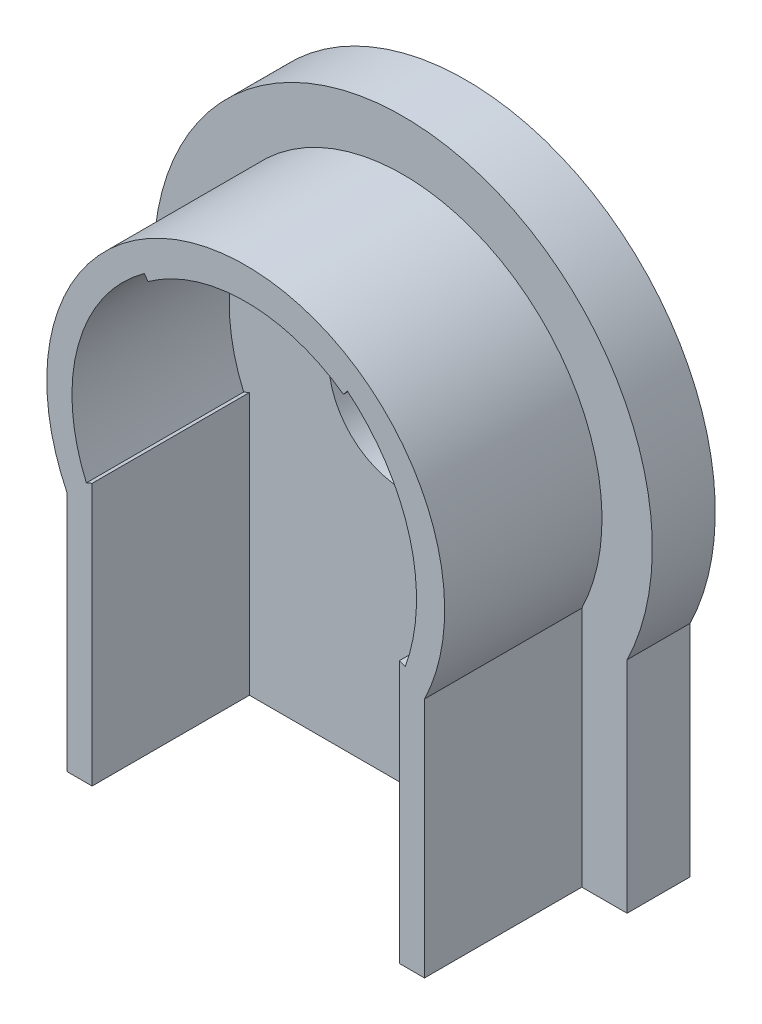
SolidWorks part; units mm, degrees
ref_plane "Alzado" through (0, 0, 0) normal (0, 0, 1) x (1, 0, 0)
ref_plane "Planta" through (0, 0, 0) normal (0, 1, 0) x (1, 0, 0)
ref_plane "Vista lateral" through (0, 0, 0) normal (1, 0, 0) x (0, 0, -1)
sketch "Croquis1" plane through (0, 0, 0) normal (0, 0, 1) x (1, 0, 0)
  line L0 (-7.75, -16.5939) -> (7.75, -16.5939)
  line L1 (-7.75, -16.5939) -> (-7.75, -8.4659)
  line L2 (7.75, -16.5939) -> (7.75, -8.2)
  line L4 (-7.75, -8.4659) -> (-7.75, -3.3658)
  line L5 (7.75, -8.2) -> (7.75, -3.3658)
  line L6 (-9.02, -8.4659) -> (-9.02, -4.4019)
  line L7 (9.02, -16.5939) -> (9.02, -8.2)
  line L9 (-9.02, -16.5939) -> (-9.02, -8.4659)
  line L10 (9.02, -8.2) -> (9.02, -4.4019)
  line L11 (-9.02, -8.4659) -> (-9.02, -3.3658) construction
  line L12 (-7.75, -16.5939) -> (-9.02, -16.5939)
  line L13 (7.75, -16.5939) -> (9.02, -16.5939)
  line L14 (-9.02, -17.8639) -> (-9.02, -8.4659) construction
  line L15 (-9.02, -17.8639) -> (9.02, -17.8639) construction
  line L16 (9.02, -17.8639) -> (9.02, -8.2) construction
  line L17 (0, 0) -> (0, -33.1879) construction
  arc A0 (7.75, -3.3658) -> (-7.75, -3.3658) centre (0, 0) ccw
  arc A1 (9.02, -4.4019) -> (-9.02, -4.4019) centre (0, 0) ccw
  circle A2 centre (0, 0) radius 8.4493 construction
  circle A3 centre (0, 0) radius 10.0368 construction
  point P5 (0, -8.4493)
  point P18 (0, -16.5939)
  dimension "D1" = 16.8986
  dimension "D3" = 15.5
  dimension "D4" = 8.128
  dimension "D5" = 1.27
  dimension "D6" = 12.192
  dimension "D2" = 1.5875
extrude "Saliente-Extruir1" add sketch "Croquis1" along normal blind 7.9375 contours L10 A1 L6 L9 L12 L1 L4 A0 L5 L2 L13 L7 region at (-8.385, -16.2605, 0)
sketch "Croquis4" plane through (0, 0, 0) normal (0, 0, 1) x (1, 0, 0)
  line L0 (-11.3027, -5.5159) -> (-11.3027, -16.5939)
  line L1 (11.3027, -5.5159) -> (11.3027, -16.5939)
  line L2 (9.02, -16.5939) -> (11.3027, -16.5939)
  line L3 (-9.02, -16.5939) -> (-11.3027, -16.5939)
  line L5 (9.02, -4.4019) -> (9.02, -16.5939)
  line L6 (-9.02, -16.5939) -> (9.02, -16.5939)
  circle A0 centre (0, 0) radius 3.75
  arc A2 (11.3027, -5.5159) -> (-11.3027, -5.5159) centre (0, 0) ccw
  arc A3 (11.3027, -5.5159) -> (-11.3027, -5.5159) centre (0, 0) ccw
  dimension "D2" = 7.5
  dimension "D1" = 2.54
extrude "Saliente-Extruir5" add sketch "Croquis4" against normal blind 3.175 contours L1 A3 L0 L3 L6 L2 region at (0, 12.1916, 0)
ref_axis "Eje1" through (0, 0, 7.9375) along (0, 0, -1)
sketch "Croquis6" plane through (0, 0, 7.9375) normal (0, 0, 1) x (1, 0, 0)
  line L0 (0, 10.0368) -> (0, 6.8618) construction
  line L1 (0, 6.8618) -> (4.9302, 6.8618) construction
  line L2 (0, 6.8618) -> (-4.9302, 6.8618) construction
  line L3 (-8.0412, -3.4922) -> (-7.75, -3.3658)
  line L4 (7.75, -3.3658) -> (8.0485, -3.474)
  line L5 (-4.9302, 6.8618) -> (-5.1154, 7.1197)
  line L6 (4.9302, 6.8618) -> (5.131, 7.1077)
  arc A0 (9.02, -4.4019) -> (-9.02, -4.4019) centre (0, 0) ccw construction
  arc A1 (7.75, -3.3658) -> (-7.75, -3.3658) centre (0, 0) ccw construction
  arc A2 (7.75, -3.3658) -> (-7.75, -3.3658) centre (0, 0) ccw construction
  arc A3 (-7.75, -3.3658) -> (-4.9302, 6.8618) centre (0, 0) cw
  arc A4 (7.75, -3.3658) -> (4.9302, 6.8618) centre (-0.8693, -0.2397) ccw
  arc A5 (-8.0412, -3.4922) -> (-5.1154, 7.1197) centre (0, 0) cw
  arc A6 (8.0485, -3.474) -> (5.131, 7.1077) centre (-0.8693, -0.2397) ccw
  dimension "D1" = 3.175
  dimension "D2" = 0.3175
  dimension "D3" = 0.3175
extrude "Cortar-Extruir2" cut sketch "Croquis6" against normal up to surface (7.9375 mm away) up to face at (3.75, 0, 0)
sketch "Croquis5" plane through (0, 0, 0) normal (0, 0, 1) x (1, 0, 0)
  line L2 (6.8546, -3.041) -> (8.0485, -3.474)
  line L3 (7.0514, 1.9441) -> (8.2757, 2.2817)
  arc A3 (8.0485, -3.474) -> (8.2757, 2.2817) centre (-0.8693, -0.2397) ccw
  arc A4 (8.0485, -3.474) -> (5.131, 7.1077) centre (-0.8693, -0.2397) ccw construction
  arc A5 (6.8546, -3.041) -> (7.0514, 1.9441) centre (-0.8693, -0.2397) ccw
  dimension "D1" = 1.27
extrude "Cortar-Extruir1" cut sketch "Croquis5" against normal blind 1.7145
